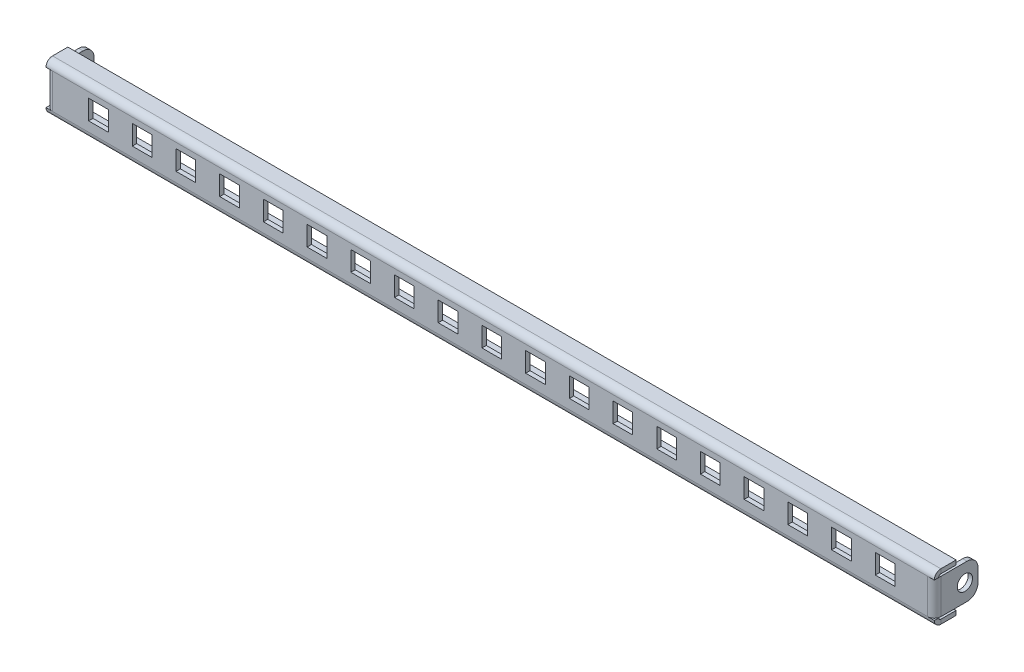
SolidWorks part; units mm, degrees
note: The reader was unsure of these and kept them because the rebuilt part matched: thickness of "基体-法兰1", "边线-法兰1", "边线-法兰2", "钣金6", "钣金7", "钣金8", "钣金9", "钣金10", "钣金11"; flange length of "边线-法兰1", "边线-法兰2".
material "普通碳钢"
ref_plane "前视基准面" through (0, 0, 0) normal (0, 0, 1) x (1, 0, 0)
ref_plane "上视基准面" through (0, 0, 0) normal (0, 1, 0) x (1, 0, 0)
ref_plane "右视基准面" through (0, 0, 0) normal (1, 0, 0) x (0, 0, -1)
sketch "草图1" plane through (0, 0, 0) normal (0, 0, 1) x (1, 0, 0)
  line L1 (-203.25, 11) -> (203.25, 11)
  line L2 (-203.25, 11) -> (-203.25, -11)
  line L3 (-203.25, -11) -> (203.25, -11)
  line L4 (203.25, 11) -> (203.25, -11)
  line L5 (-203.25, 11) -> (203.25, -11) construction
  line L6 (-203.25, -11) -> (203.25, 11) construction
  point P0 (0, 0)
  dimension "D1" = 406.5
  dimension "D2" = 22
base flange "基体-法兰1" sketch "草图1" thickness 2 reverse thickness direction no parameters "D1"=1
edge flange "边线-法兰1" sketch "草图10" flange profiles "草图10", "草图11" flange angle 90 flange length 10 flange position material inside bend radius 1 thickness 2 relief rectangular parameters "D6"=10, "D8"=0.2
sketch "草图10" plane through (0, -11, -2) normal (0, 1, 0) x (1, 0, 0)
  line L1 (203.25, 0) -> (-203.25, 0) construction
  line L2 (-203.25, 0) -> (-203.25, 8)
  line L3 (-203.25, 8) -> (203.25, 8)
  line L4 (203.25, 8) -> (203.25, 0)
  line L5 (203.25, 0) -> (-203.25, 0)
  dimension "D1" = 8
sketch "草图11" plane through (0, 11, -2) normal (0, -1, 0) x (-1, 0, 0)
  line L0 (203.25, 0) -> (-203.25, 0) construction
  line L1 (203.25, 0) -> (-203.25, 0)
  line L2 (203.25, 0) -> (203.25, 8)
  line L3 (203.25, 8) -> (-203.25, 8)
  line L4 (-203.25, 8) -> (-203.25, 0)
bend "边线折弯1" bend radius 1 bend angle 90 parameters "D5"=1
bend "边线折弯2" bend radius 1 bend angle 90 parameters "D5"=2
edge flange "边线-法兰2" sketch "草图16" flange profiles "草图16", "草图17" flange angle 90 flange length 20 flange position material inside bend radius 1 thickness 2 relief none parameters "D6"=10, "D8"=0.2
sketch "草图16" plane through (-203.25, 0, -2) normal (1, 0, 0) x (0, -1, 0)
  line L1 (8, 0) -> (-8, 0) construction
  line L2 (-8, 0) -> (-8, 18)
  line L3 (-8, 18) -> (8, 18)
  line L4 (8, 18) -> (8, 0)
  line L5 (8, 0) -> (-8, 0)
  dimension "D1" = 18
sketch "草图17" plane through (203.25, 0, -2) normal (-1, 0, 0) x (0, 1, 0)
  line L0 (8, 0) -> (-8, 0) construction
  line L1 (8, 0) -> (-8, 0)
  line L2 (8, 0) -> (8, 18)
  line L3 (8, 18) -> (-8, 18)
  line L4 (-8, 18) -> (-8, 0)
bend "边线折弯3" bend radius 1 bend angle 90 parameters "D5"=3
bend "边线折弯4" bend radius 1 bend angle 90 parameters "D5"=4
sketch "草图18" plane through (0, 0, 0) normal (0, 0, 1) x (1, 0, 0)
  line L0 (203.25, 11) -> (-203.25, 11) construction
  line L5 (-183.75, 5.5) -> (-174.75, 5.5)
  line L6 (-183.75, 5.5) -> (-183.75, -3.5)
  line L7 (-183.75, -3.5) -> (-174.75, -3.5)
  line L8 (-174.75, 5.5) -> (-174.75, -3.5)
  line L9 (-183.75, 5.5) -> (-174.75, -3.5) construction
  line L10 (-183.75, -3.5) -> (-174.75, 5.5) construction
  line L12 (0, 0) -> (0, 52.0184) construction
  line L13 (-203.25, -8) -> (-203.25, 8) construction
  point P0 (-179.25, 1)
  dimension "D1" = 19.5
  dimension "D2" = 9
  dimension "D3" = 9
  dimension "D4" = 10
extrude "切除-拉伸1" cut sketch "草图18" against normal blind 10 normal cut yes
pattern_linear "阵列(线性)1" count 19 spacing 20 along (1, 0, 0) of "切除-拉伸1"
fillet "圆角1" radius 5 4 edges at (202.25, -8, -20) (202.25, 8, -20) (-202.25, 8, -20) (-202.25, -8, -20)
sketch "草图19" plane through (203.25, 0, 0) normal (1, 0, 0) x (0, 0, -1)
  line L0 (-6.0129, 0) -> (22.4684, 0) construction
  line L1 (20, 3) -> (20, -3) construction
  circle A1 centre (14, 0) radius 3.5
  dimension "D3" = 7
  dimension "D4" = 6
extrude "切除-拉伸2" cut sketch "草图19" against normal through all normal cut yes
sketch "折弯-线1" [suppressed] plane through (0, 0, 0) normal (0, 1, 0) x (1, 0, 0)
sketch "边界框1" [suppressed] plane through (0, 0, 0) normal (0, 1, 0) x (1, 0, 0)
sheet metal parameters "钣金6" thickness 2 parameters "D1"=1, "D7"=1
flat pattern "平板型式6" [suppressed]
sketch "折弯-线2" plane through (0, 0, 0) normal (0, 1, 0) x (1, 0, 0)
sketch "边界框2" [suppressed] plane through (0, 0, 0) normal (0, 1, 0) x (1, 0, 0)
sheet metal parameters "钣金7" thickness 2 parameters "D1"=1, "D7"=1
flat pattern "平板型式6" [suppressed]
sketch "折弯-线2" plane through (0, 0, 0) normal (0, 1, 0) x (1, 0, 0)
sketch "边界框2" [suppressed] plane through (0, 0, 0) normal (0, 1, 0) x (1, 0, 0)
bend of the flat pattern "展开-<边线折弯1>1"
bend of the flat pattern "展开-<边线折弯2>1"
sheet metal parameters "钣金8" thickness 2 parameters "D1"=1, "D7"=1
flat pattern "平板型式6" [suppressed]
sketch "折弯-线2" plane through (0, 0, 0) normal (0, 1, 0) x (1, 0, 0)
sketch "边界框2" [suppressed] plane through (0, 0, 0) normal (0, 1, 0) x (1, 0, 0)
bend of the flat pattern "展开-<边线折弯1>1"
bend of the flat pattern "展开-<边线折弯2>1"
bend of the flat pattern "展开-<边线折弯3>1"
bend of the flat pattern "展开-<边线折弯4>1"
sheet metal parameters "钣金9" thickness 2 parameters "D1"=1, "D7"=1
flat pattern "平板型式6" [suppressed]
sketch "折弯-线2" plane through (0, 0, 0) normal (0, 1, 0) x (1, 0, 0)
sketch "边界框2" [suppressed] plane through (0, 0, 0) normal (0, 1, 0) x (1, 0, 0)
bend of the flat pattern "展开-<边线折弯1>1"
bend of the flat pattern "展开-<边线折弯2>1"
bend of the flat pattern "展开-<边线折弯3>1"
bend of the flat pattern "展开-<边线折弯4>1"
sheet metal parameters "钣金10" thickness 2 parameters "D1"=1, "D7"=1
flat pattern "平板型式6"
sketch "折弯-线2" plane through (0, 0, 0) normal (0, 0, 1) x (1, 0, 0)
  line L0 (294.1, -47.5) -> (294.1, 47.5) construction
  line L1 (-294.1, 47.5) -> (-294.1, -47.5) construction
  line L2 (295, 49.1) -> (-295, 49.1) construction
  line L3 (-295, -49.1) -> (295, -49.1) construction
  line L4 (294.1, -47.5) -> (294.1, 47.5) construction
  line L5 (-294.1, 47.5) -> (-294.1, -47.5) construction
  line L6 (295, 49.1) -> (-295, 49.1) construction
  line L7 (-295, -49.1) -> (295, -49.1) construction
sketch3d "边界框2" [suppressed]
  line L0 (-313.2, -56.2, 0) -> (313.2, -56.2, 0) construction
  line L1 (-313.2, 56.2, 0) -> (313.2, 56.2, 0) construction
  line L2 (-313.2, -56.2, 0) -> (-313.2, 56.2, 0) construction
  line L3 (313.2, -56.2, 0) -> (313.2, 56.2, 0) construction
bend of the flat pattern "展开-<边线折弯1>1"
bend of the flat pattern "展开-<边线折弯2>1"
bend of the flat pattern "展开-<边线折弯3>1"
bend of the flat pattern "展开-<边线折弯4>1"
sheet metal parameters "钣金11" thickness 2 parameters "D1"=1, "D7"=1
flat pattern "平板型式6"
sketch "折弯-线2" plane through (0, 0, 0) normal (0, 0, 1) x (1, 0, 0)
  line L0 (294.1, -47.5) -> (294.1, 47.5) construction
  line L1 (-294.1, 47.5) -> (-294.1, -47.5) construction
  line L2 (295, 49.1) -> (-295, 49.1) construction
  line L3 (-295, -49.1) -> (295, -49.1) construction
  line L4 (294.1, -47.5) -> (294.1, 47.5) construction
  line L5 (-294.1, 47.5) -> (-294.1, -47.5) construction
  line L6 (295, 49.1) -> (-295, 49.1) construction
  line L7 (-295, -49.1) -> (295, -49.1) construction
sketch3d "边界框2" [suppressed]
  line L0 (-313.2, -56.2, 0) -> (313.2, -56.2, 0) construction
  line L1 (-313.2, 56.2, 0) -> (313.2, 56.2, 0) construction
  line L2 (-313.2, -56.2, 0) -> (-313.2, 56.2, 0) construction
  line L3 (313.2, -56.2, 0) -> (313.2, 56.2, 0) construction
bend of the flat pattern "展开-<边线折弯1>1"
bend of the flat pattern "展开-<边线折弯2>1"
bend of the flat pattern "展开-<边线折弯3>1"
bend of the flat pattern "展开-<边线折弯4>1"
